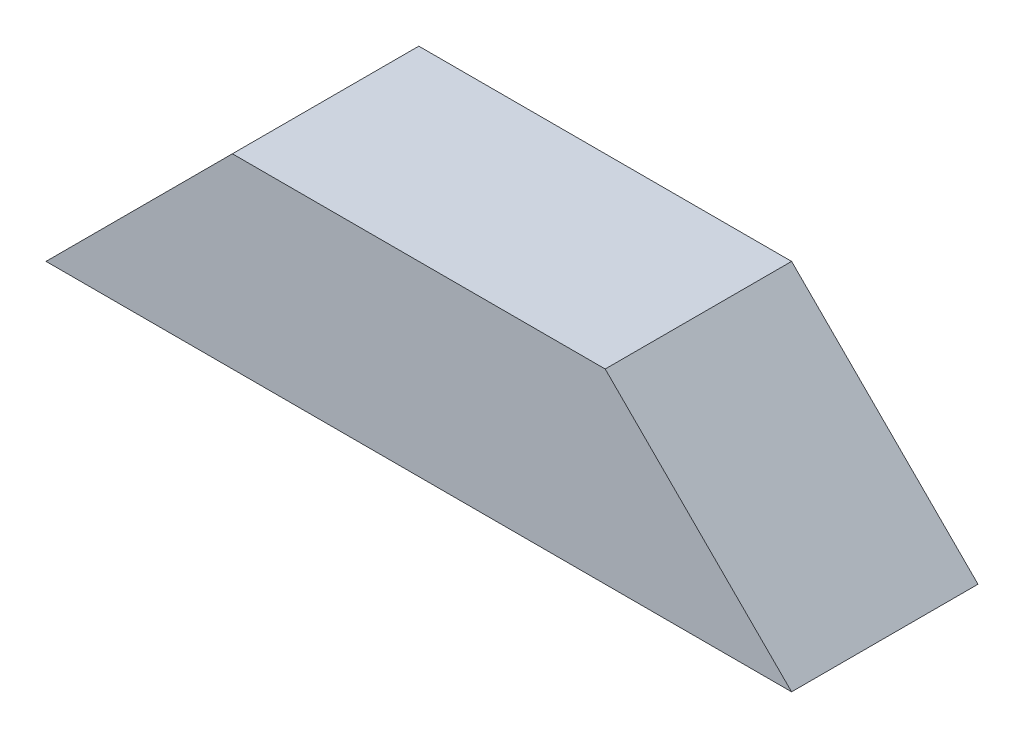
SolidWorks part; units mm, degrees
ref_plane "Plan de face" through (0, 0, 0) normal (0, 0, 1) x (1, 0, 0)
ref_plane "Plan de dessus" through (0, 0, 0) normal (0, 1, 0) x (1, 0, 0)
ref_plane "Plan de droite" through (0, 0, 0) normal (1, 0, 0) x (0, 0, -1)
sketch "Esquisse1" plane through (0, 0, 0) normal (0, 0, 1) x (1, 0, 0)
  line L1 (0, 0) -> (80, 0)
  line L2 (0, 0) -> (0, 20)
  line L3 (0, 20) -> (80, 20)
  line L4 (80, 0) -> (80, 20)
  dimension "D1" = 80
  dimension "D2" = 20
extrude "Boss.-Extru.1" add sketch "Esquisse1" along normal blind 20
sketch "Esquisse2" plane through (0, 0, 20) normal (0, 0, 1) x (1, 0, 0)
  line L0 (40, 0) -> (40, 20) construction
  line L9 (0, 0) -> (80, 0) construction
  line L10 (80, 20) -> (0, 20) construction
  line L11 (0, 20) -> (20, 20)
  line L12 (20, 20) -> (0, 0)
  line L13 (0, 0) -> (0, 20)
  line L14 (80, 0) -> (80, 20)
  line L15 (60, 20) -> (80, 0)
  line L16 (80, 20) -> (60, 20)
  point P9 (0, 30)
  dimension "D1" = 45
extrude "Enlèv. mat.-Extru.1" cut sketch "Esquisse2" against normal through all both and the other way through all
